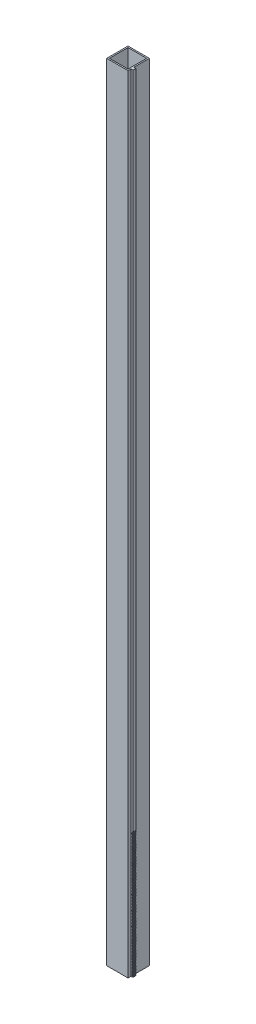
SolidWorks part; units mm, degrees
ref_plane "Front Plane" through (0, 0, 0) normal (0, 0, 1) x (1, 0, 0)
ref_plane "Top Plane" through (0, 0, 0) normal (0, 1, 0) x (1, 0, 0)
ref_plane "Right Plane" through (0, 0, 0) normal (1, 0, 0) x (0, 0, -1)
sketch "Sketch1" plane through (0, 0, 0) normal (0, 1, 0) x (1, 0, 0)
  line L1 (0, 0) -> (-50.8, 0)
  line L2 (0, 0) -> (0, -50.8)
  line L3 (0, -50.8) -> (-50.8, -50.8)
  line L4 (-50.8, 0) -> (-50.8, -50.8)
  dimension "D1" = 50.8
  dimension "D2" = 50.8
extrude "Boss-Extrude1" add sketch "Sketch1" along normal blind 1873.25
shell "Shell1" thickness 3.175 removed face at (-25.4, 0, 25.4) removed face at (-25.4, 1873.25, 25.4)
ref_plane "Plane1" through (0, 1873.25, 50.8) normal (0, 0, -1) x (-1, 0, 0)
sketch "Sketch3" plane through (0, 0, 0) normal (1, 0, 0) x (0, 0, -1)
  line L0 (-50.8, 1873.25) -> (0, 1873.25) construction
  line L1 (-43.8889, 1873.25) -> (-36.8889, 1873.25)
  line L2 (-43.8889, 1873.25) -> (-43.8889, 0)
  line L3 (-43.8889, 0) -> (-36.8889, 0)
  line L4 (-36.8889, 1873.25) -> (-36.8889, 0)
  line L5 (-50.8, 0) -> (0, 0) construction
  line L6 (-50.8, 1873.25) -> (-50.8, 0) construction
  dimension "D1" = 6.9111
  dimension "D2" = 7
extrude "Boss-Extrude2" add sketch "Sketch3" along normal blind 5
sketch "Sketch4" plane through (0, 0, 36.8889) normal (0, 0, -1) x (-1, 0, 0)
  line L0 (-5, 1.5) -> (-3, 2)
  line L1 (-5, 0) -> (-5, 1873.25) construction
  line L2 (-3, 2) -> (-3, 3)
  line L3 (-3, 3) -> (-5, 3.5)
  line L4 (-5, 3.5) -> (-5, 1.5)
  dimension "D1" = 1
  dimension "D2" = 2
  dimension "D3" = 0.5
  dimension "D4" = 2
  dimension "D5" = 1.5
extrude "Cut-Extrude1" cut sketch "Sketch4" against normal up to next
pattern_linear "LPattern1" count 100 spacing 3 along (0, 1, 0) count 2 spacing 3 along (0, -1, 0) of "Cut-Extrude1"
